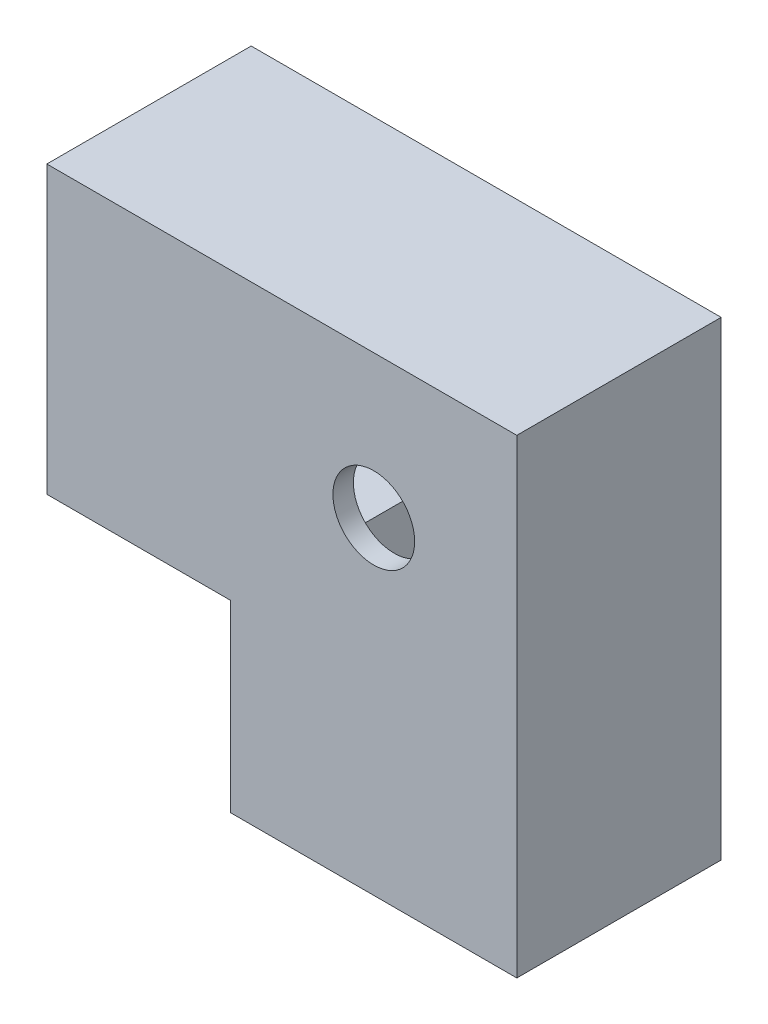
SolidWorks part; units mm, degrees
ref_plane "Alzado" through (0, 0, 0) normal (0, 0, 1) x (1, 0, 0)
ref_plane "Planta" through (0, 0, 0) normal (0, 1, 0) x (1, 0, 0)
ref_plane "Vista lateral" through (0, 0, 0) normal (1, 0, 0) x (0, 0, -1)
sketch "Croquis1" plane through (0, 0, 0) normal (0, 0, 1) x (1, 0, 0)
  line L0 (117743.4169, 152337.8366) -> (131743.4169, 152337.8366)
  line L1 (131743.4169, 152337.8366) -> (131743.4169, 161337.8366)
  line L2 (131743.4169, 161337.8366) -> (140743.4169, 161337.8366)
  line L3 (140743.4169, 161337.8366) -> (140743.4169, 175337.8366)
  line L4 (140743.4169, 175337.8366) -> (117743.4169, 175337.8366)
  line L5 (117743.4169, 175337.8366) -> (117743.4169, 152337.8366)
  line L6 (118743.4169, 152337.8366) -> (118743.4169, 166437.8366)
  line L7 (118743.4169, 174337.8366) -> (122843.4169, 174337.8366)
  line L8 (130743.4169, 152337.8366) -> (130743.4169, 162337.8366)
  line L9 (140743.4169, 162337.8366) -> (130743.4169, 162337.8366)
  line L10 (131743.4169, 161337.8366) -> (108743.4169, 161337.8366)
  line L11 (108743.4169, 161337.8366) -> (108743.4169, 162337.8366)
  line L12 (108743.4169, 162337.8366) -> (122843.4169, 162337.8366)
  line L13 (131743.4169, 161337.8366) -> (131743.4169, 184337.8366)
  line L14 (131743.4169, 184337.8366) -> (130743.4169, 184337.8366)
  line L15 (130743.4169, 184337.8366) -> (130743.4169, 170237.8366)
  line L16 (118743.4169, 174337.8366) -> (118743.4169, 184337.8366)
  line L17 (118743.4169, 184337.8366) -> (117743.4169, 184337.8366)
  line L18 (117743.4169, 184337.8366) -> (117743.4169, 175337.8366)
  line L19 (118743.4169, 174337.8366) -> (108743.4169, 174337.8366)
  line L20 (108743.4169, 174337.8366) -> (108743.4169, 175337.8366)
  line L21 (108743.4169, 175337.8366) -> (117743.4169, 175337.8366)
  line L22 (108743.4169, 174337.8366) -> (108743.4169, 162337.8366)
  line L23 (118743.4169, 184337.8366) -> (130743.4169, 184337.8366)
  line L24 (122743.4169, 174237.8366) -> (122743.4169, 172837.8366)
  line L25 (124243.4169, 171337.8366) -> (125243.4169, 171337.8366)
  line L26 (126743.4169, 172837.8366) -> (126743.4169, 174237.8366)
  line L27 (118843.4169, 170337.8366) -> (120243.4169, 170337.8366)
  line L28 (121743.4169, 168837.8366) -> (121743.4169, 167837.8366)
  line L29 (120243.4169, 166337.8366) -> (118843.4169, 166337.8366)
  line L30 (130643.4169, 170337.8366) -> (129243.4169, 170337.8366)
  line L31 (127743.4169, 168837.8366) -> (127743.4169, 167837.8366)
  line L32 (129243.4169, 166337.8366) -> (130643.4169, 166337.8366)
  line L33 (122743.4169, 162437.8366) -> (122743.4169, 163837.8366)
  line L34 (124243.4169, 165337.8366) -> (125243.4169, 165337.8366)
  line L35 (126743.4169, 163837.8366) -> (126743.4169, 162337.8366)
  line L36 (121743.4169, 168337.8366) -> (127743.4169, 168337.8366) construction
  line L37 (118743.4169, 170237.8366) -> (120243.4169, 170237.8366)
  line L38 (118843.4169, 174237.8366) -> (122743.4169, 174237.8366)
  line L39 (121643.4169, 168837.8366) -> (121643.4169, 167837.8366)
  line L40 (118843.4169, 162437.8366) -> (118843.4169, 166337.8366)
  line L41 (118843.4169, 162437.8366) -> (122743.4169, 162437.8366)
  line L42 (130643.4169, 174237.8366) -> (130643.4169, 170337.8366)
  line L43 (120243.4169, 166437.8366) -> (118743.4169, 166437.8366)
  line L44 (118743.4169, 174237.8366) -> (140743.4169, 174237.8366) construction
  line L45 (122843.4169, 162337.8366) -> (122843.4169, 163837.8366)
  line L46 (124243.4169, 165237.8366) -> (125243.4169, 165237.8366)
  line L47 (126643.4169, 163837.8366) -> (126643.4169, 162337.8366)
  line L48 (130743.4169, 170237.8366) -> (129243.4169, 170237.8366)
  line L49 (127843.4169, 168837.8366) -> (127843.4169, 167837.8366)
  line L50 (129243.4169, 166437.8366) -> (130743.4169, 166437.8366)
  line L51 (122843.4169, 174337.8366) -> (122843.4169, 172837.8366)
  line L52 (124243.4169, 171437.8366) -> (125243.4169, 171437.8366)
  line L53 (126643.4169, 172837.8366) -> (126643.4169, 174337.8366)
  line L54 (130643.4169, 166337.8366) -> (130643.4169, 162437.8366)
  line L55 (130743.4169, 166437.8366) -> (130743.4169, 162337.8366)
  line L56 (129243.4169, 166337.8366) -> (130743.4169, 166337.8366) construction
  line L57 (130743.4169, 170337.8366) -> (129243.4169, 170337.8366) construction
  line L58 (126643.4169, 174337.8366) -> (140743.4169, 174337.8366)
  line L59 (118743.4169, 174337.8366) -> (140743.4169, 174337.8366) construction
  line L60 (126743.4169, 174237.8366) -> (130643.4169, 174237.8366)
  line L61 (126743.4169, 172837.8366) -> (126743.4169, 174337.8366) construction
  line L62 (122743.4169, 174337.8366) -> (122743.4169, 172837.8366) construction
  line L63 (118743.4169, 170237.8366) -> (118743.4169, 174337.8366)
  line L64 (118843.4169, 170337.8366) -> (118843.4169, 174237.8366)
  line L65 (118743.4169, 170337.8366) -> (120243.4169, 170337.8366) construction
  line L66 (120243.4169, 166337.8366) -> (118743.4169, 166337.8366) construction
  line L67 (126743.4169, 162437.8366) -> (130643.4169, 162437.8366)
  line L68 (122743.4169, 162337.8366) -> (122743.4169, 163837.8366) construction
  line L69 (126643.4169, 162337.8366) -> (130743.4169, 162337.8366)
  arc A0 (125243.4169, 165337.8366) -> (126743.4169, 163837.8366) centre (125243.4169, 163837.8366) cw
  arc A1 (122743.4169, 163837.8366) -> (124243.4169, 165337.8366) centre (124243.4169, 163837.8366) cw
  arc A2 (127743.4169, 167837.8366) -> (129243.4169, 166337.8366) centre (129243.4169, 167837.8366) ccw
  arc A3 (129243.4169, 170337.8366) -> (127743.4169, 168837.8366) centre (129243.4169, 168837.8366) ccw
  arc A4 (125243.4169, 171337.8366) -> (126743.4169, 172837.8366) centre (125243.4169, 172837.8366) ccw
  arc A5 (122743.4169, 172837.8366) -> (124243.4169, 171337.8366) centre (124243.4169, 172837.8366) ccw
  arc A6 (120243.4169, 170337.8366) -> (121743.4169, 168837.8366) centre (120243.4169, 168837.8366) cw
  arc A7 (121743.4169, 167837.8366) -> (120243.4169, 166337.8366) centre (120243.4169, 167837.8366) cw
  circle A8 centre (124743.4169, 168337.8366) radius 2000
  arc A9 (120243.4169, 170237.8366) -> (121643.4169, 168837.8366) centre (120243.4169, 168837.8366) cw
  arc A10 (121643.4169, 167837.8366) -> (120243.4169, 166437.8366) centre (120243.4169, 167837.8366) cw
  arc A11 (122843.4169, 163837.8366) -> (124243.4169, 165237.8366) centre (124243.4169, 163837.8366) cw
  arc A12 (125243.4169, 165237.8366) -> (126643.4169, 163837.8366) centre (125243.4169, 163837.8366) cw
  arc A13 (129243.4169, 170237.8366) -> (127843.4169, 168837.8366) centre (129243.4169, 168837.8366) ccw
  arc A14 (127843.4169, 167837.8366) -> (129243.4169, 166437.8366) centre (129243.4169, 167837.8366) ccw
  arc A15 (122843.4169, 172837.8366) -> (124243.4169, 171437.8366) centre (124243.4169, 172837.8366) ccw
  arc A16 (125243.4169, 171437.8366) -> (126643.4169, 172837.8366) centre (125243.4169, 172837.8366) ccw
  circle A17 centre (124743.4169, 168337.8366) radius 1900
  point P34 (126743.4169, 163087.8366)
  point P39 (126743.4169, 165337.8366)
  point P42 (122743.4169, 165337.8366)
  point P45 (127743.4169, 166337.8366)
  point P48 (127743.4169, 170337.8366)
  point P51 (126743.4169, 171337.8366)
  point P54 (122743.4169, 171337.8366)
  point P57 (121743.4169, 170337.8366)
  point P60 (121743.4169, 166337.8366)
  dimension "D21" = 1500
  dimension "D22" = 4000
  dimension "D1" = 12000
  dimension "D2" = 1000
  dimension "D3" = 1000
  dimension "D4" = 1000
  dimension "D5" = 1000
  dimension "D6" = 12000
  dimension "D7" = 9000
  dimension "D8" = 9000
  dimension "D9" = 9000
  dimension "D10" = 9000
  dimension "D11" = 4000
  dimension "D12" = 4000
  dimension "D13" = 4000
  dimension "D14" = 4000
  dimension "D18" = 4000
  dimension "D19" = 4000
  dimension "D20" = 3000
  dimension "D23" = 100
  dimension "D24" = 100
  dimension "D25" = 100
  dimension "D26" = 100
ref_plane "Plano1" through (0, 161337.8366, 0) normal (0, 1, 0) x (1, 0, 0)
ref_plane "Plano2" through (0, 175337.8366, 0) normal (0, 1, 0) x (1, 0, 0)
ref_plane "Plano3" through (117743.4169, 0, 0) normal (1, 0, 0) x (0, 0, -1)
ref_plane "Plano4" through (131743.4169, 0, 0) normal (1, 0, 0) x (0, 0, -1)
ref_plane "Plano5" through (113243.4169, 0, 0) normal (1, 0, 0) x (0, 0, -1)
ref_plane "Plano6" through (0, 179837.8366, 0) normal (0, 1, 0) x (1, 0, 0)
ref_plane "Plano7" through (136243.4169, 0, 0) normal (1, 0, 0) x (0, 0, -1)
ref_plane "Plano8" through (0, 156837.8366, 0) normal (0, 1, 0) x (1, 0, 0)
sketch "Croquis2" plane through (0, 156837.8366, 0) normal (0, 1, 0) x (1, 0, 0)
  line L0 (117743.4169, 0) -> (131743.4169, 0) construction
  line L1 (117743.4169, 0) -> (131743.4169, 0)
  line L2 (131743.4169, 0) -> (131743.4169, 8000)
  line L3 (131743.4169, 8000) -> (130743.4169, 8000)
  line L4 (130743.4169, 8000) -> (130743.4169, 1000)
  line L5 (130743.4169, 1000) -> (118743.4169, 1000)
  line L6 (118743.4169, 1000) -> (118743.4169, 8000)
  line L7 (118743.4169, 8000) -> (117743.4169, 8000)
  line L8 (117743.4169, 8000) -> (117743.4169, 0)
  spline S0 degree 2 poles (130743.4169, 8000) (128761.6752, 7234.3483) (128743.4169, 1000) knots 0 0 0 0.590989 0.590989 0.590989
  spline S1 degree 2 poles (118743.4169, 8000) (120739.8111, 7120.5788) (120743.4169, 1000) knots 0 0 0 0.514461 0.514461 0.514461
  dimension "D1" = 1000
  dimension "D2" = 1000
  dimension "D3" = 1000
  dimension "D4" = 7000
  dimension "D5" = 7000
  dimension "D6" = 2000
  dimension "D7" = 2000
sketch "Croquis3" plane through (0, 179837.8366, 0) normal (0, 1, 0) x (1, 0, 0)
  line L0 (118743.4169, 1000) -> (118743.4169, 8000) construction
  line L1 (130743.4169, 1000) -> (118743.4169, 1000) construction
  line L2 (130743.4169, 8000) -> (130743.4169, 1000) construction
  line L3 (118743.4169, 1000) -> (118743.4169, 8000)
  line L4 (130743.4169, 1000) -> (118743.4169, 1000)
  line L5 (130743.4169, 8000) -> (130743.4169, 1000)
  parabola Q0 (118743.4169, 8000) -> (120743.4169, 1000) focus (118361.6774, 7241.9739) apex (118662.5082, 8033.1777) construction
  parabola Q1 (130743.4169, 8000) -> (128743.4169, 1000) focus (131040.6578, 7282.3326) apex (130778.3168, 8013.005) construction
  parabola Q2 (118743.4169, 8000) -> (120743.4169, 1000) focus (118361.6774, 7241.9739) apex (118662.5082, 8033.1777)
  parabola Q3 (130743.4169, 8000) -> (128743.4169, 1000) focus (131040.6578, 7282.3326) apex (130778.3168, 8013.005)
sketch "Croquis4" plane through (113243.4169, 0, 0) normal (1, 0, 0) x (0, 0, -1)
  line L0 (0, 174337.8366) -> (0, 162337.8366) construction
  line L1 (0, 174337.8366) -> (0, 162337.8366)
  line L2 (0, 162337.8366) -> (8000, 162337.8366)
  line L3 (0, 174337.8366) -> (8000, 174337.8366)
  spline S0 degree 2 poles (8000, 162337.8366) (6698.659, 164240.8241) (0, 164337.8366) knots 0 0 0 0.70753 0.70753 0.70753
  spline S1 degree 2 poles (8000, 174337.8366) (6599.8546, 172118.7435) (0, 172337.8366) knots 0 0 0 0.648378 0.648378 0.648378
  dimension "D1" = 8000
  dimension "D2" = 2000
  dimension "D3" = 2000
sketch "Croquis5" plane through (136243.4169, 0, 0) normal (1, 0, 0) x (0, 0, -1)
  line L0 (0, 162337.8366) -> (8000, 162337.8366) construction
  line L1 (0, 174337.8366) -> (0, 162337.8366) construction
  line L2 (0, 174337.8366) -> (8000, 174337.8366) construction
  line L3 (0, 162337.8366) -> (8000, 162337.8366)
  line L4 (0, 174337.8366) -> (0, 162337.8366)
  line L5 (0, 174337.8366) -> (8000, 174337.8366)
  parabola Q0 (8000, 162337.8366) -> (0, 164337.8366) focus (7402.6379, 161620.0634) apex (8222.0253, 161894.2353) construction
  parabola Q1 (8000, 174337.8366) -> (0, 172337.8366) focus (7073.338, 175098.4045) apex (8142.0414, 174597.2807) construction
  parabola Q2 (8000, 162337.8366) -> (0, 164337.8366) focus (7402.6379, 161620.0634) apex (8222.0253, 161894.2353)
  parabola Q3 (8000, 174337.8366) -> (0, 172337.8366) focus (7073.338, 175098.4045) apex (8142.0414, 174597.2807)
extrude "Saliente-Extruir1" add sketch "Croquis1" against normal blind 1000 contours L15 L58 L13 L4 | L19 L16 L4 L5 | L21 L20 L19 L5 | L19 L22 L12 L5 | L12 L11 L10 L5 | L12 L5 L10 L6 | L6 L10 L5 L0 | L8 L10 L6 L0 | L1 L10 L8 L0 | L10 L13 L9 L8 | A12 L46 A11 L45 L12 L6 L10 L8 L69 L47 | L49 A14 L50 L55 L9 L13 L58 L15 L48 A13 | L52 A16 L53 L58 L15 L4 L16 L7 L51 A15 | A10 L39 A9 L37 L63 L19 L5 L12 L6 L43 | L28 A7 L29 L40 L41 L33 A1 L34 A0 L35 L67 L54 L32 A2 L31 A3 L30 L42 L60 L26 A4 L25 A5 L24 L38 L64 L27 A6 A8 | A16 L52 A15 L51 L7 L63 L37 A9 L39 A10 L43 L6 L12 L45 A11 L46 A12 L47 L69 L35 A0 L34 A1 L33 L41 L40 L29 A7 L28 A6 L27 L64 L38 L24 A5 L25 A4 L26 L60 L42 L30 A3 L31 A2 L32 L54 L67 L55 region at (118243.4169, 156837.8366, 0) region at (124743.4169, 156837.8366, 0) region at (113243.4169, 161837.8366, 0) region at (118243.4169, 161837.8366, 0) region at (131243.4169, 156837.8366, 0) region at (124743.4169, 162689.636, 0) region at (113243.4169, 168337.8366, 0) region at (119095.2163, 168337.8366, 0) region at (131243.4169, 161837.8366, 0) region at (126910.2941, 163137.8366, 0) region at (118760.3875, 164387.8366, 0) region at (113243.4169, 174837.8366, 0) region at (118243.4169, 174837.8366, 0) region at (130391.6175, 168337.8366, 0) region at (124743.4169, 173986.0372, 0) region at (131243.4169, 174837.8366, 0)
extrude "Saliente-Extruir2" add sketch "Croquis1<6>" against normal blind 10000 contours L15 L58 L13 L4 | L19 L16 L4 L5 | L21 L20 L19 L5 | L12 L11 L10 L5 | L12 L5 L10 L6 | L6 L10 L5 L0 | L1 L10 L8 L0 | L10 L13 L9 L8 | L52 A16 L53 L58 L15 L4 L16 L7 L51 A15 | L49 A14 L50 L55 L9 L13 L58 L15 L48 A13 region at (118243.4169, 156837.8366, 0) region at (113243.4169, 161837.8366, 0) region at (118243.4169, 161837.8366, 0) region at (131243.4169, 156837.8366, 0) region at (131243.4169, 161837.8366, 0) region at (113243.4169, 174837.8366, 0) region at (118243.4169, 174837.8366, 0) region at (130391.6175, 168337.8366, 0) region at (124743.4169, 173986.0372, 0) region at (131243.4169, 174837.8366, 0)
sketch "Croquis1<6>" plane through (0, 0, 0) normal (0, 0, 1) x (1, 0, 0) same geometry as "Croquis1"
extrude "Saliente-Extruir3" add sketch "Croquis2" along normal blind 500 and the other way blind 500 contours L4 S0 L5 | S1 L6 L5 region at (119605.9639, 156837.8366, -3955.1574) region at (129880.6924, 156837.8366, -3967.5864)
extrude "Saliente-Extruir5" add sketch "Croquis4" along normal blind 500 and the other way blind 500 contours L2 S0 L1 | S1 L3 L1 region at (113243.4169, 173449.622, -3378.0839) region at (113243.4169, 163181.6256, -3312.204)
